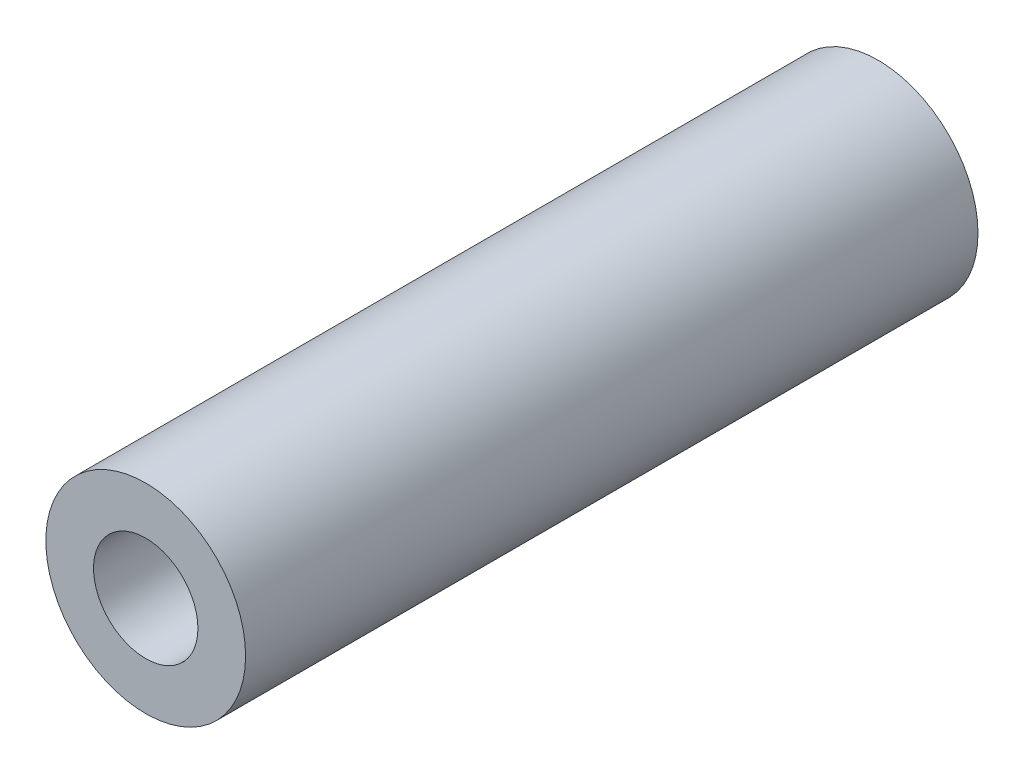
SolidWorks part; units mm, degrees
material "6061-T6 (SS)"
ref_plane "Front Plane" through (0, 0, 0) normal (0, 0, 1) x (1, 0, 0)
ref_plane "Top Plane" through (0, 0, 0) normal (0, 1, 0) x (1, 0, 0)
ref_plane "Right Plane" through (0, 0, 0) normal (1, 0, 0) x (0, 0, -1)
sketch "Sketch1" plane through (0, 0, 0) normal (0, 0, 1) x (1, 0, 0)
  circle A0 centre (0, 0) radius 2.4892
  circle A1 centre (0, 0) radius 4.7625
  dimension "D1" = 4.9784
  dimension "D2" = 9.525
extrude "Boss-Extrude1" add sketch "Sketch1" along normal mid plane 34.925
